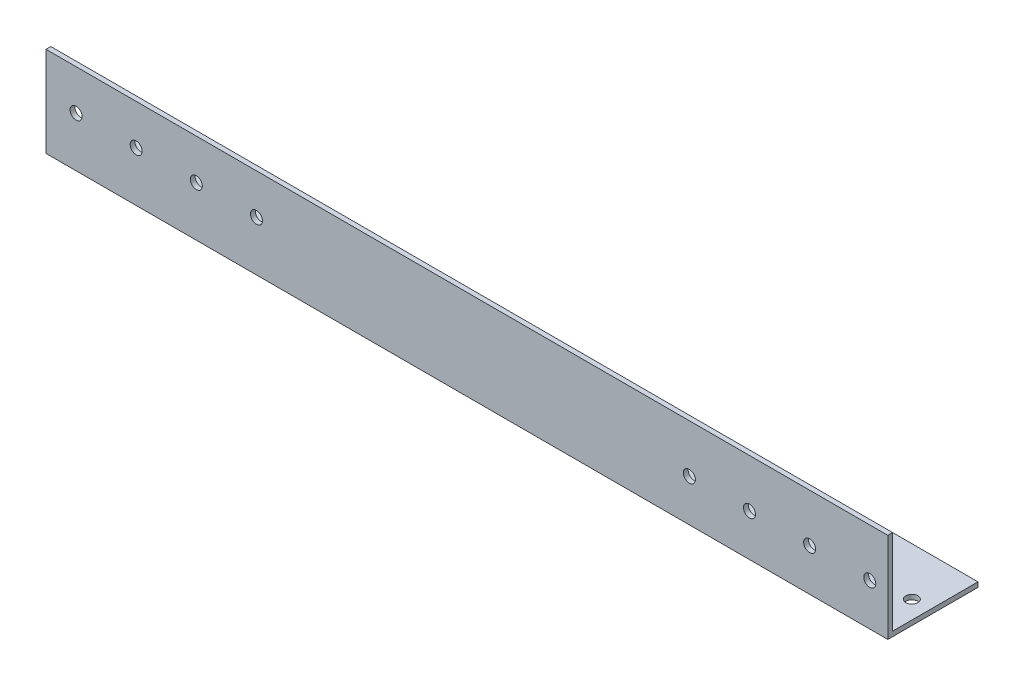
SolidWorks part; units mm, degrees
ref_plane "Спереди" through (0, 0, 0) normal (0, 0, 1) x (1, 0, 0)
ref_plane "Сверху" through (0, 0, 0) normal (0, 1, 0) x (1, 0, 0)
ref_plane "Справа" through (0, 0, 0) normal (1, 0, 0) x (0, 0, -1)
sketch "Эскиз1" plane through (0, 0, 0) normal (1, 0, 0) x (0, 0, -1)
  line L0 (0, 0) -> (0, 75)
  line L1 (0, 0) -> (75, 0)
extrude "Вытянуть-Тонкостенный1" add sketch "Эскиз1" along normal blind 700 thin thin type one direction reverse wall 4
sketch "Эскиз2" plane through (0, 0, 0) normal (0, 0, 1) x (1, 0, 0)
  circle A0 centre (25, 41.5) radius 5
  circle A1 centre (75, 41.5) radius 5
  circle A2 centre (125, 41.5) radius 5
  circle A3 centre (175, 41.5) radius 5
  circle A4 centre (535, 35) radius 5
  circle A5 centre (585, 35) radius 5
  circle A6 centre (635, 35) radius 5
  circle A7 centre (685, 35) radius 5
  point P2 (0, 0)
  dimension "D1" = 4
extrude "Вырез-Вытянуть1" cut sketch "Эскиз2" against normal blind 10
sketch "Эскиз3" plane through (0, 0, 0) normal (0, -1, 0) x (1, 0, 0)
  circle A0 centre (25, -41.5) radius 5
  circle A1 centre (75, -41.5) radius 5
  circle A2 centre (125, -41.5) radius 5
  circle A3 centre (175, -41.5) radius 5
  circle A4 centre (535, -35) radius 5
  circle A5 centre (585, -35) radius 5
  circle A6 centre (635, -35) radius 5
  circle A7 centre (685, -35) radius 5
  point P2 (0, 0)
  point P9 (0, 0)
  dimension "D1" = 4
extrude "Вырез-Вытянуть2" cut sketch "Эскиз3" against normal blind 10
